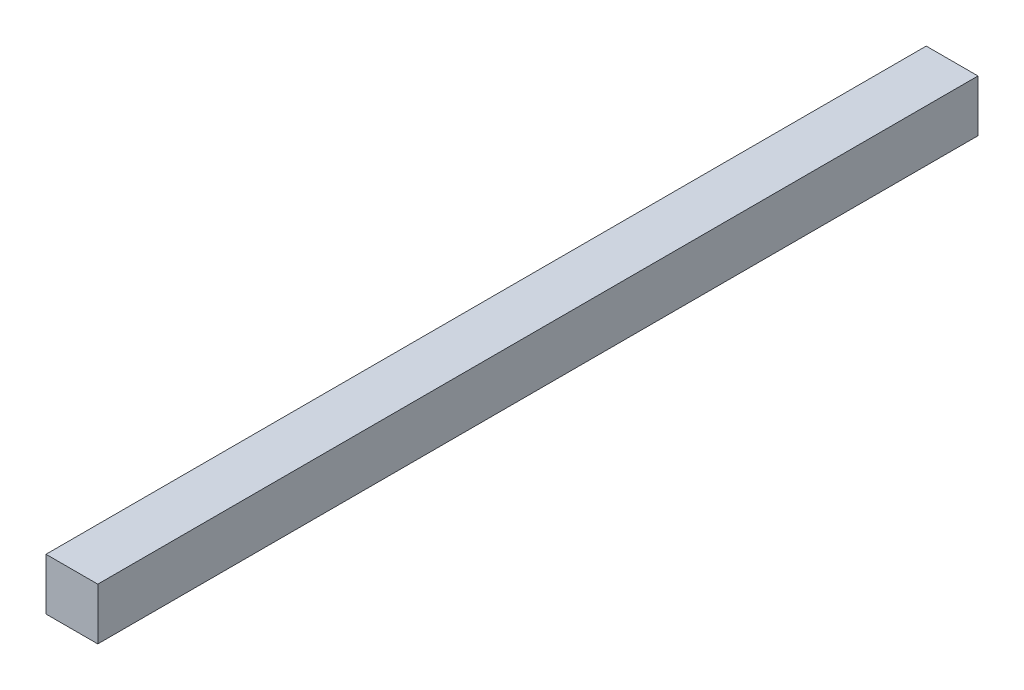
SolidWorks part; units mm, degrees
ref_plane "Plan de face" through (0, 0, 0) normal (0, 0, 1) x (1, 0, 0)
ref_plane "Plan de dessus" through (0, 0, 0) normal (0, 1, 0) x (1, 0, 0)
ref_plane "Plan de droite" through (0, 0, 0) normal (1, 0, 0) x (0, 0, -1)
sketch "Esquisse1" plane through (0, 0, 0) normal (0, 0, 1) x (1, 0, 0)
  line L0 (-5, 5) -> (5, -5) construction
  line L1 (-5, 5) -> (5, 5)
  line L2 (-5, 5) -> (-5, -5)
  line L3 (-5, -5) -> (5, -5)
  line L4 (5, 5) -> (5, -5)
  dimension "D1" = 10
extrude "Boss.-Extru.1" add sketch "Esquisse1" along normal mid plane 170
